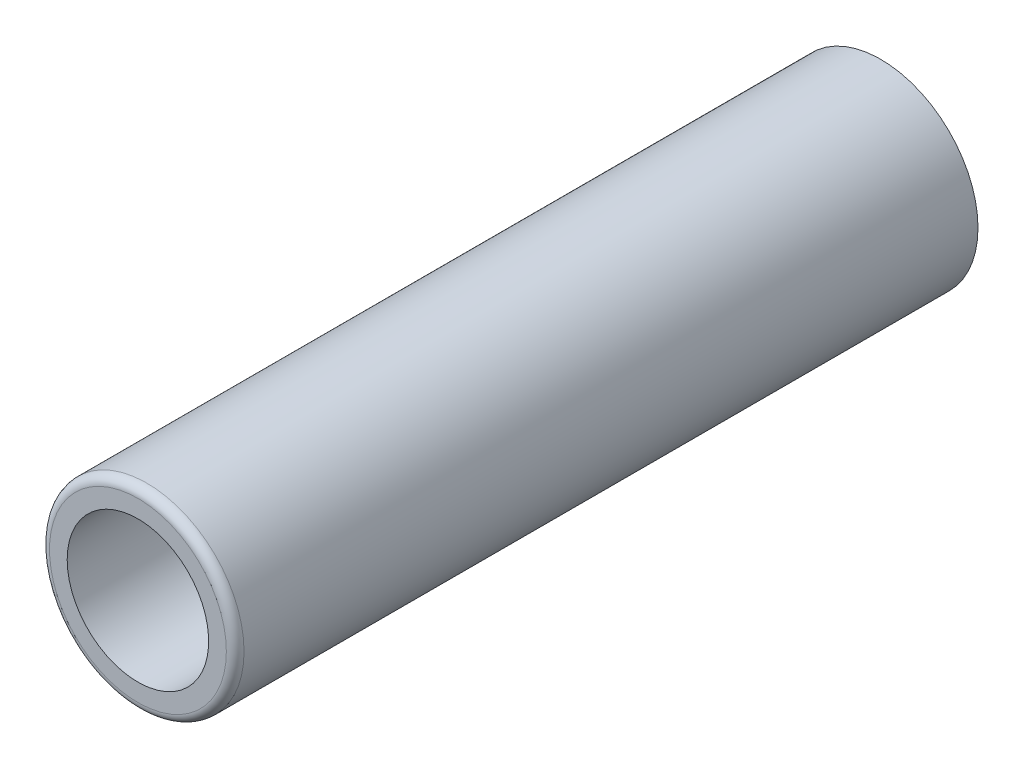
SolidWorks part; units mm, degrees
material "Acciaio al carbonio semplice"
ref_plane "Piano frontale" through (0, 0, 0) normal (0, 0, 1) x (1, 0, 0)
ref_plane "Piano superiore" through (0, 0, 0) normal (0, 1, 0) x (1, 0, 0)
ref_plane "Piano destro" through (0, 0, 0) normal (1, 0, 0) x (0, 0, -1)
sketch "Schizzo1" plane through (0, 0, 0) normal (0, 0, 1) x (1, 0, 0)
  circle A0 centre (0, 0) radius 55
  dimension "D1" = 110
extrude "Estrusione-Estrusione1" add sketch "Schizzo1" along normal blind 420
sketch "Schizzo2" plane through (0, 0, 0) normal (0, 0, -1) x (-1, 0, 0)
  circle A0 centre (0, 0) radius 40
  dimension "D1" = 80
extrude "Taglio-Estrusione1" cut sketch "Schizzo2" against normal through all
fillet "Raccordo1" radius 5 1 edges at (55, 0, 420)
